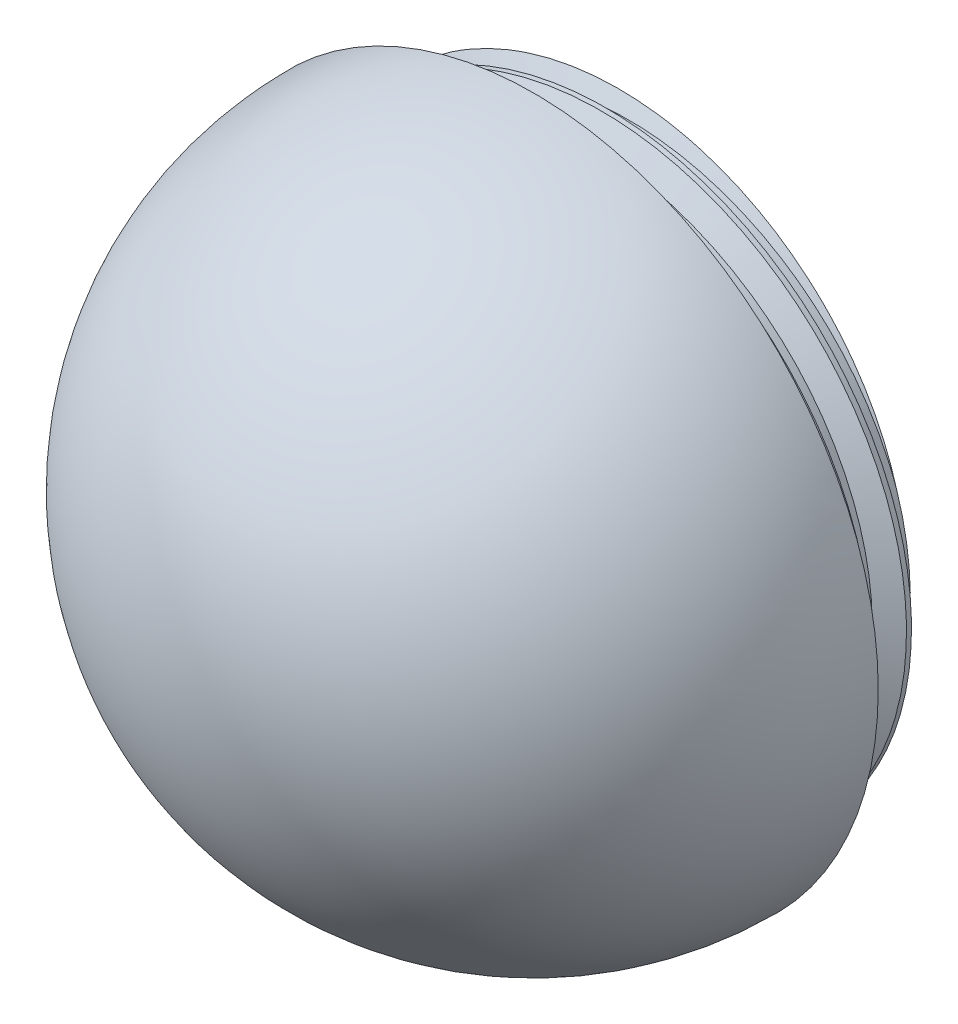
SolidWorks part; units mm, degrees
ref_plane "Front Plane" through (0, 0, 0) normal (0, 0, 1) x (1, 0, 0)
ref_plane "Top Plane" through (0, 0, 0) normal (0, 1, 0) x (1, 0, 0)
ref_plane "Right Plane" through (0, 0, 0) normal (1, 0, 0) x (0, 0, -1)
sketch "Sketch1" plane through (0, 0, 0) normal (0, 0, 1) x (1, 0, 0)
  line L0 (0, 21.5) -> (0, -21.5)
  arc A0 (0, 21.5) -> (0, -21.5) centre (0, 0) cw
  dimension "D1" = 43
revolve "Revolve1" add sketch "Sketch1" angle 180 about L0
shell "Shell1" thickness 1
sketch "Sketch2" plane through (0, 0, 0) normal (0, 0, -1) x (-1, 0, 0)
  circle A0 centre (0, 0) radius 20.5 construction
  circle A1 centre (0, 0) radius 20.5
  circle A2 centre (0, 0) radius 15.5
  dimension "D1" = 5
extrude "Boss-Extrude1" add sketch "Sketch2" against normal up to next
sketch "Sketch4" plane through (0, 0, 0) normal (0, 0, -1) x (-1, 0, 0)
  circle A0 centre (0, 0) radius 15.5 construction
  circle A1 centre (0, 0) radius 15.5
  circle A2 centre (0, 0) radius 17.5
  dimension "D1" = 2
extrude "Boss-Extrude2" add sketch "Sketch4" along normal blind 6
thread "Thread1" pitch 2.5 start angle 0, offset 2, length 8, pitch 2.5, diameter 35
ref_plane "Plane1" through (17.5, 0, -8) normal (0, -1, 0) x (1, 0, 0)
sketch "Thread Profile1" plane through (17.5, 0, -8) normal (0, -1, 0) x (1, 0, 0)
  line L0 (0, 0) -> (0, 2.5) construction
  line L1 (0, 0) -> (1.3532, 0.7812)
  line L2 (1.3532, 0.7812) -> (1.3532, 1.0937)
  line L3 (1.3532, 1.0937) -> (0, 1.875)
  line L4 (1.3532, 0.9375) -> (0, 0.9375) construction
  line L11 (0, 0) -> (0, 1.875)
  point P2 (0, 0)
  dimension "Pitch" = 2.5
  dimension "Profile_Angle" = 60
  dimension "Profile_Land" = 0.3125
  dimension "Profile_Height" = 1.3532
